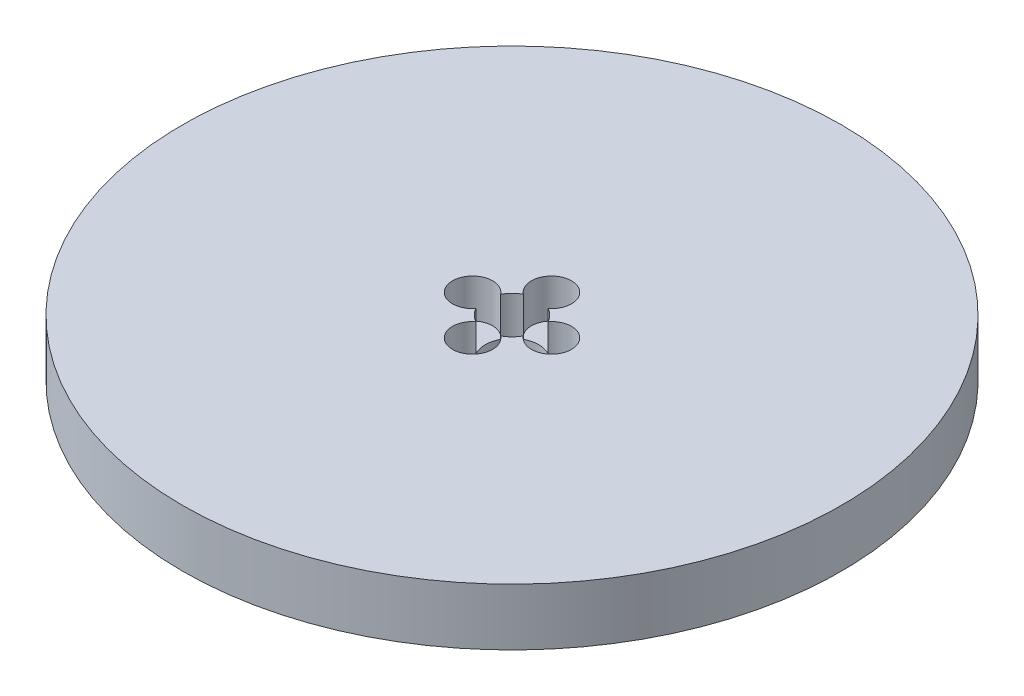
SolidWorks part; units mm, degrees
ref_plane "Front Plane" through (0, 0, 0) normal (0, 0, 1) x (1, 0, 0)
ref_plane "Top Plane" through (0, 0, 0) normal (0, 1, 0) x (1, 0, 0)
ref_plane "Right Plane" through (0, 0, 0) normal (1, 0, 0) x (0, 0, -1)
sketch "Sketch1" plane through (0, 0, 0) normal (0, 1, 0) x (1, 0, 0)
  circle A0 centre (0, 0) radius 92.5
  dimension "FLANGE_OD" = 185
extrude "Boss-Extrude1" add sketch "Sketch1" along normal blind 16
sketch "Sketch2" plane through (0, 0, 0) normal (0, 1, 0) x (1, 0, 0)
  circle A0 centre (0, 0) radius 7.5
  dimension "BORE_D" = 15
extrude "Cut-Extrude1" cut sketch "Sketch2" along normal through all
sketch "Sketch3" plane through (0, 16, 0) normal (0, 1, 0) x (1, 0, 0)
  circle A0 centre (0, 0) radius 11.0698 construction
  circle A1 centre (-11.0698, 0) radius 5.6187
  dimension "BOLT_D" = 11.2374
  dimension "BOLT_PCD" = 22.1396
extrude "Cut-Extrude2" cut sketch "Sketch3" against normal blind 10.9473
pattern_circular "CirPattern1" count 4 over 360 about axis through (0, 0, 0) along (0, 1, 0) of "Cut-Extrude2"
